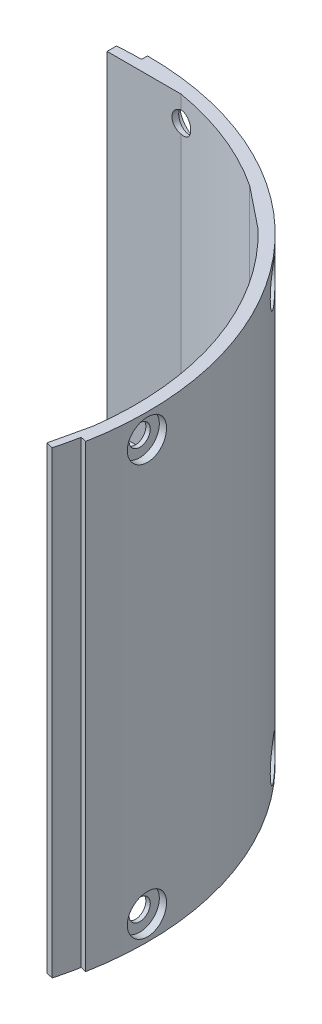
SolidWorks part; units mm, degrees
ref_plane "Спереди" through (0, 0, 0) normal (0, 0, 1) x (1, 0, 0)
ref_plane "Сверху" through (0, 0, 0) normal (0, 1, 0) x (1, 0, 0)
ref_plane "Справа" through (0, 0, 0) normal (1, 0, 0) x (0, 0, -1)
sketch "Эскиз2" plane through (0, 0, 0) normal (0, 1, 0) x (1, 0, 0)
  line L0 (0, -1000) -> (0, 49000) construction
  line L1 (-8.2529, 48.3) -> (8.2529, 48.3) construction
  line L2 (33.9524, 35.3303) -> (27.0476, 40.8587) construction
  line L3 (48.5627, -6.5315) -> (46.5973, -15.1557) construction
  line L4 (-3.9968, 48.3) -> (8.2529, 48.3)
  line L5 (33.9524, 35.3303) -> (27.0476, 40.8587)
  line L6 (48.5627, -6.5315) -> (46.5973, -15.1557) construction
  line L7 (-3.9968, 48.3) -> (-3.9968, 49.84)
  line L10 (-8.2529, 48.3) -> (-3.9968, 48.3) construction
  line L11 (0, 50) -> (0, 51)
  line L12 (0, 0) -> (47.58, -10.8436) construction
  line L16 (47.58, -10.8436) -> (49.725, -11.3324) construction
  line L17 (47.1356, -12.7936) -> (48.5627, -6.5315)
  line L19 (47.1356, -12.7936) -> (48.2666, -13.0514)
  line L20 (50.1312, -9.3737) -> (49.1554, -9.1514)
  circle A0 centre (0, 0) radius 51 construction
  arc A1 (50.1312, -9.3737) -> (0, 51) centre (0, 0) ccw
  circle A2 centre (0, 0) radius 51 construction
  arc A3 (48.5627, -6.5315) -> (33.9524, 35.3303) centre (0, 0) ccw construction
  arc A4 (0, 51) -> (0, -51) centre (0, 0) ccw construction
  arc A5 (48.5627, -6.5315) -> (33.9524, 35.3303) centre (0, 0) ccw
  arc A6 (8.2529, 48.3) -> (27.0476, 40.8587) centre (0, 0) cw
  arc A7 (0, -51) -> (49.725, -11.3324) centre (0, 0) ccw construction
  arc A8 (49.725, -11.3324) -> (50.1312, -9.3737) centre (0, 0) ccw construction
  arc A9 (0, 50) -> (-3.9968, 49.84) centre (0, 0) ccw
  arc A10 (49.1554, -9.1514) -> (48.2666, -13.0514) centre (0, 0) cw
  dimension "D1" = 3.9968
  dimension "D2" = 1
  dimension "D3" = 4
extrude "Бобышка-Вытянуть2" add sketch "Эскиз2" along normal up to surface (76 mm away)
ref_plane "Плоскость4" through (12.7171, 0, -36.1271) normal (-0.332, 0, 0.9433) x (0.9433, 0, 0.332)
sketch "Эскиз7" plane through (12.7171, 0, -36.1271) normal (-0.332, 0, 0.9433) x (0.9433, 0, 0.332)
  line L5 (-8.2529, 17) -> (5.2529, 17) construction
  line L6 (-8.2529, 17) -> (5.2529, 17) construction
  line L7 (8.2529, 14) -> (5.2529, 17) construction
  line L8 (8.2529, 14) -> (5.2529, 17)
  line L9 (-8.2529, 0) -> (8.2529, 0) construction
  line L16 (-8.2529, 0) -> (8.2529, 0)
  line L17 (-8.2529, 76) -> (-8.2529, 0) construction
  line L18 (-8.2529, 17) -> (-8.2529, 0) construction
  line L19 (8.7529, 14.2071) -> (8.7529, 0)
  line L20 (8.7529, 14.2071) -> (5.46, 17.5)
  line L21 (8.2529, 14) -> (8.2529, 0) construction
  line L22 (8.2529, 14) -> (8.2529, 0) construction
  line L23 (-8.7529, 17.5) -> (5.46, 17.5)
  line L24 (-8.7529, 17.5) -> (-8.7529, 0)
  line L25 (-8.7529, 0) -> (-8.2529, 0)
  line L26 (8.2529, 0) -> (8.7529, 0)
  dimension "D1" = 0.5
extrude "Вырез-Вытянуть3" cut sketch "Эскиз7" against normal through all contours L16 L26 L19 L20 L23 L24 L25 region at (12.587, 8.6121, -36.1729)
sketch "Эскиз9" plane through (0, 0, -48.3) normal (0, 0, 1) x (1, 0, 0)
  line L4 (8.7529, 0) -> (8.7529, 17.5)
  line L6 (-3.9968, 76) -> (-3.9968, 0) construction
  line L7 (-3.9968, 19.5032) -> (-3.9968, 0)
  line L8 (-3.9968, 76) -> (-3.9968, 19.5032) construction
  line L9 (-3.9968, 19.5032) -> (-6.5, 17) construction
  line L10 (-8.2529, 0) -> (-3.9968, 0) construction
  line L11 (8.7529, 17.5) -> (6.7071, 17.5)
  line L12 (6.7071, 17.5) -> (3.7071, 20.5)
  line L13 (3.7071, 20.5) -> (-3.7071, 20.5)
  line L14 (-8.2529, 0) -> (8.2529, 0)
  line L15 (8.2529, 0) -> (8.2529, 17)
  line L24 (8.2529, 17) -> (6.5, 17)
  line L25 (6.5, 17) -> (3.5, 20)
  line L26 (3.5, 20) -> (-3.5, 20)
  line L28 (-3.7071, 20.5) -> (-3.9968, 20.2104)
  line L29 (-3.5, 20) -> (-6.5, 17)
  line L30 (-6.5, 17) -> (-8.2529, 17)
  line L31 (-8.2529, 17) -> (-8.2529, 0)
  line L32 (-3.9968, 0) -> (8.2529, 0)
  line L33 (8.2529, 0) -> (8.2529, 17) construction
  line L34 (8.2529, 17) -> (6.5, 17) construction
  line L35 (6.5, 17) -> (3.5, 20) construction
  line L36 (3.5, 20) -> (-3.5, 20) construction
  line L37 (-3.5, 20) -> (-3.9968, 19.5032)
  line L38 (-6.5, 17) -> (-8.2529, 17) construction
  line L39 (-8.2529, 17) -> (-8.2529, 0) construction
  line L40 (-3.9968, 19.5032) -> (-3.9968, 20.2104)
  line L41 (-3.9968, 20.2104) -> (-4.3503, 19.8568) construction
  line L42 (-3.7071, 20.5) -> (-4.3503, 19.8568) construction
  line L43 (8.7529, 0) -> (8.2529, 0)
  line M9 (-8.2529, 0) -> (8.2529, 0)
  line M10 (8.2529, 0) -> (8.2529, 17)
  line M11 (8.2529, 17) -> (6.5, 17)
  line M12 (6.5, 17) -> (3.5, 20)
  line M13 (3.5, 20) -> (-3.5, 20)
  line M14 (-3.5, 20) -> (-6.5, 17)
  dimension "D1" = 0
  dimension "D2" = 0.5
extrude "Вырез-Вытянуть4" cut sketch "Эскиз9" against normal through all contours L7 M14 M9 M10 M11 M12 M13 | L43 L4 L11 L12 L13 L28 L40 M14 M13 M12 M11 M10 region at (8.5029, 0.2414, -48.3) region at (1.9493, 9.6325, -48.3)
sketch "Эскиз10" plane through (0, 12, 0) normal (0, 1, 0) x (1, 0, 0)
  line L0 (-3.9968, 48.3) -> (8.2529, 48.3) construction
  line L1 (-3.9968, 48.3) -> (8.2529, 48.3)
  line L2 (23.8222, 42.8194) -> (20.9924, 43.8155) construction
  line L3 (8.2529, 48.3) -> (20.9924, 43.8155) construction
  line L4 (23.8222, 42.8194) -> (20.9924, 43.8155)
  line L5 (8.2529, 48.3) -> (20.9924, 43.8155)
  line L7 (23.4097, 41.9045) -> (20.6603, 42.8723)
  line L8 (8.082, 47.3) -> (20.6603, 42.8723)
  line L9 (-3.9968, 47.3) -> (8.082, 47.3)
  line L10 (-3.9968, 47.3) -> (-3.9968, 48.3)
  line L11 (26.4956, 40.0248) -> (27.0476, 40.8587) construction
  line L12 (26.4956, 40.0248) -> (28.4646, 39.7241)
  line L13 (27.0476, 40.8587) -> (33.9524, 35.3303) construction
  line L14 (28.4646, 39.7241) -> (27.0476, 40.8587) construction
  line L15 (28.4646, 39.7241) -> (27.0476, 40.8587) construction
  line L16 (28.4646, 39.7241) -> (27.0476, 40.8587)
  arc A0 (27.0476, 40.8587) -> (8.2529, 48.3) centre (0, 0) ccw construction
  arc A1 (27.0476, 40.8587) -> (23.8222, 42.8194) centre (0, 0) ccw
  arc A2 (23.8222, 42.8194) -> (8.2529, 48.3) centre (0, 0) ccw construction
  arc A3 (26.4956, 40.0248) -> (23.4097, 41.9045) centre (0, 0) ccw
  dimension "D2" = 30
  dimension "D1" = 1
extrude "Бобышка-Вытянуть7" add sketch "Эскиз10" along normal blind 10
sketch "Эскиз13" plane through (0, 22, 0) normal (0, 1, 0) x (1, 0, 0)
  line L0 (23.8222, 42.8194) -> (8.2529, 48.3) construction
  line L1 (23.8222, 42.8194) -> (8.2529, 48.3)
  arc A0 (27.0476, 40.8587) -> (8.2529, 48.3) centre (0, 0) ccw construction
  arc A1 (27.0476, 40.8587) -> (8.2529, 48.3) centre (0, 0) ccw
  line M2 (23.8222, 42.8194) -> (8.2529, 48.3)
extrude "Бобышка-Вытянуть8" add sketch "Эскиз13" against normal up to surface (4.5 mm away) contours A1 M2 region at (16.1306, 22, -45.824) up to face at (13.0597, 17.5, -47.6707)
sketch "Эскиз14" plane through (0, 17.5, 0) normal (0, -1, 0) x (1, 0, 0)
  line L0 (21.3189, -44.1192) -> (21.1877, -43.7468)
  line L1 (21.1877, -43.7468) -> (8.2529, -48.3) construction
  line L4 (21.9869, -46.0171) -> (21.3189, -44.1192)
  line L5 (23.8222, -42.8194) -> (8.2529, -48.3)
  line L6 (8.2529, -48.3) -> (6.7071, -48.3)
  line L7 (6.7071, -48.3) -> (6.7071, -50.557)
  line L8 (21.9869, -46.0171) -> (21.3189, -44.1192)
  line L9 (23.8222, -42.8194) -> (21.1877, -43.7468)
  line L10 (8.2529, -48.3) -> (6.7071, -48.3) construction
  line L11 (6.7071, -48.3) -> (6.7071, -50.557) construction
  arc A2 (6.7071, -50.557) -> (21.9869, -46.0171) centre (0, 0) ccw
  arc A3 (21.3189, -44.1192) -> (23.8222, -42.8194) centre (0, 0) ccw
  arc A4 (6.7071, -50.557) -> (21.9869, -46.0171) centre (0, 0) ccw construction
  arc A5 (21.3189, -44.1192) -> (23.8222, -42.8194) centre (0, 0) ccw
  dimension "D1" = 0
extrude "Бобышка-Вытянуть9" add sketch "Эскиз14" along normal up to surface contours A5 L9 L0 up to face at (23.2708, 15.6229, -44.011)
chamfer "Фаска1" distance 1 angle 45 4 edges at (2.0426, 22, -47.3) (15.7459, 22, -44.6022) (24.9703, 22, -40.9937) (27.4801, 22, -39.8745)
ref_plane "Плоскость5" through (51, 0, 0) normal (1, 0, 0) x (0, 0, -1)
sketch "Эскиз15" plane through (51, 0, 0) normal (1, 0, 0) x (0, 0, -1)
  line L0 (0, -1000) -> (0, 49000) construction
  circle A0 centre (0, 4) radius 3.25
  dimension "D1" = 6.5
  dimension "D2" = 4
extrude "Вырез-Вытянуть5" cut sketch "Эскиз15" against normal blind 1.3
sketch "Эскиз16" plane through (49.7, 0, 0) normal (1, 0, 0) x (0, 0, -1)
  circle A0 centre (0, 4) radius 3.25 construction
  circle A1 centre (0, 4) radius 3.25 construction
  circle A2 centre (0, 4) radius 1.75
  dimension "D1" = 3.5
extrude "Вырез-Вытянуть6" cut sketch "Эскиз16" against normal through all
pattern_circular "Круговой массив3" count 3 every 20 about axis through (0, 0, 0) along (0, 1, 0) skipping 1 of "Вырез-Вытянуть5", "Вырез-Вытянуть6"
sketch "Эскиз17" plane through (51, 0, 0) normal (1, 0, 0) x (0, 0, -1)
  line L0 (0, -1000) -> (0, 49000) construction
  line L1 (51, 76) -> (-9.3737, 76) construction
  circle A0 centre (0, 72) radius 3.25
  circle A1 centre (0, 4) radius 3.25 construction
  dimension "D1" = 4
extrude "Вырез-Вытянуть7" cut sketch "Эскиз17" against normal blind 1.3
sketch "Эскиз18" plane through (49.7, 0, 0) normal (1, 0, 0) x (0, 0, -1)
  circle A0 centre (0, 72) radius 3.25 construction
  circle A1 centre (0, 72) radius 3.25 construction
  circle A2 centre (0, 72) radius 1.75
  circle A3 centre (0, 4) radius 1.75 construction
extrude "Вырез-Вытянуть8" cut sketch "Эскиз18" against normal through all
pattern_circular "Круговой массив5" count 5 every 20 about axis through (0, 76, 0) along (0, 1, 0) skipping 1, 3 of "Вырез-Вытянуть8", "Вырез-Вытянуть7"
